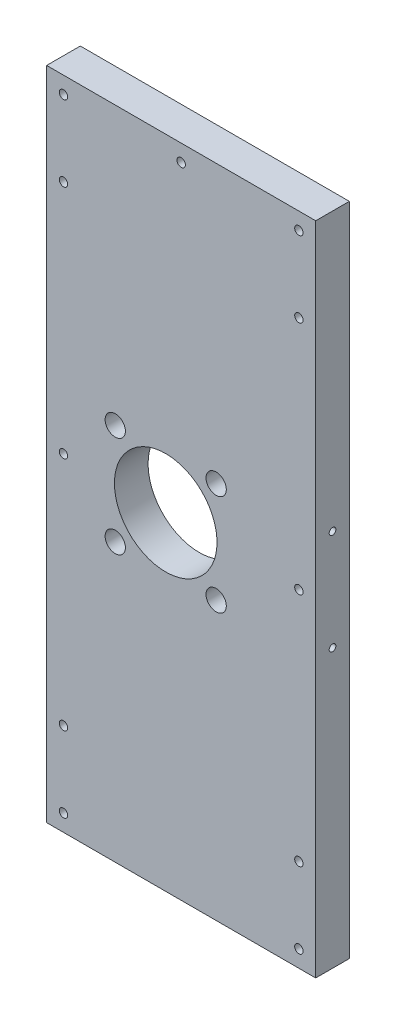
SolidWorks part; units mm, degrees
ref_plane "Ebene vorne" through (0, 0, 0) normal (0, 0, 1) x (1, 0, 0)
ref_plane "Ebene oben" through (0, 0, 0) normal (0, 1, 0) x (1, 0, 0)
ref_plane "Ebene rechts" through (0, 0, 0) normal (1, 0, 0) x (0, 0, -1)
sketch "Skizze1" plane through (0, 0, 0) normal (0, 0, 1) x (1, 0, 0)
  line L1 (-69.0594, 70.0995) -> (10.9406, 70.0995)
  line L2 (-69.0594, 70.0995) -> (-69.0594, -124.9005)
  line L3 (-69.0594, -124.9005) -> (10.9406, -124.9005)
  line L4 (10.9406, 70.0995) -> (10.9406, -124.9005)
  dimension "D1" = 195
  dimension "D2" = 80
extrude "Aufsatz-Linear austragen1" add sketch "Skizze1" against normal blind 10
sketch "Skizze2" plane through (0, 0, -10) normal (0, 0, -1) x (-1, 0, 0)
  line L0 (33.6594, 70.0995) -> (33.6594, -124.9005) construction
  line L1 (-10.9406, 70.0995) -> (69.0594, 70.0995) construction
  line L2 (69.0594, -124.9005) -> (-10.9406, -124.9005) construction
  line L3 (33.6594, -27.4005) -> (69.0594, -27.4005) construction
  line L4 (69.0594, 70.0995) -> (69.0594, -124.9005) construction
  line L5 (18.6594, -12.4005) -> (48.6594, -12.4005) construction
  line L6 (48.6594, -12.4005) -> (48.6594, -42.4005) construction
  line L7 (48.6594, -42.4005) -> (18.6594, -42.4005) construction
  line L8 (18.6594, -42.4005) -> (18.6594, -12.4005) construction
  line L9 (18.6594, -12.4005) -> (48.6594, -42.4005) construction
  circle A0 centre (18.6594, -12.4005) radius 3.015
  circle A1 centre (48.6594, -12.4005) radius 3.015
  circle A2 centre (18.6594, -42.4005) radius 3.015
  circle A3 centre (48.6594, -42.4005) radius 3.015
  circle A4 centre (33.6594, -27.4005) radius 15.25
  point P22 (33.6594, -27.4005)
  dimension "D1" = 30
  dimension "D3" = 6.03
  dimension "D2" = 30
  dimension "D4" = 35.4
extrude "Schnitt-Linear austragen1" cut sketch "Skizze2" against normal blind 10
sketch "Skizze3" plane through (0, 0, -10) normal (0, 0, -1) x (-1, 0, 0)
  line L0 (-5.9406, 65.0995) -> (64.0594, 65.0995) construction
  line L1 (29.0594, 65.0995) -> (29.0594, 70.0995) construction
  line L2 (-10.9406, 70.0995) -> (69.0594, 70.0995) construction
  line L3 (69.0594, 70.0995) -> (69.0594, -124.9005) construction
  line L4 (-5.9406, -119.9005) -> (64.0594, -119.9005) construction
  line L5 (29.0594, -119.9005) -> (29.0594, -124.9005) construction
  line L6 (69.0594, -124.9005) -> (-10.9406, -124.9005) construction
  line L7 (-5.9406, 42.5995) -> (-5.9406, -27.4005) construction
  line L8 (-5.9406, 42.5995) -> (-5.9406, 65.0995) construction
  line L9 (-5.9406, -27.4005) -> (-5.9406, -97.4005) construction
  line L10 (64.0594, 42.5995) -> (64.0594, 65.0995) construction
  line L11 (64.0594, -97.4005) -> (64.0594, -27.4005) construction
  line L12 (-5.9406, -97.4005) -> (-5.9406, -119.9005) construction
  line L13 (64.0594, -97.4005) -> (64.0594, -119.9005) construction
  line L15 (64.0594, -27.4005) -> (64.0594, 42.5995) construction
  circle A0 centre (29.0594, 65.0995) radius 2.5
  circle A1 centre (-5.9406, 65.0995) radius 2.5
  circle A2 centre (64.0594, 65.0995) radius 2.5
  circle A3 centre (29.0594, -119.9005) radius 2.5
  circle A4 centre (-5.9406, -119.9005) radius 2.5
  circle A5 centre (64.0594, -119.9005) radius 2.5
  circle A6 centre (-5.9406, 42.5995) radius 2.5
  circle A7 centre (-5.9406, -27.4005) radius 2.5
  circle A9 centre (-5.9406, -97.4005) radius 2.5
  circle A10 centre (64.0594, -97.4005) radius 2.5
  circle A12 centre (64.0594, -27.4005) radius 2.5
  circle A13 centre (64.0594, 42.5995) radius 2.5
  dimension "D3" = 5
  dimension "D1" = 5
  dimension "D2" = 5
  dimension "D4" = 70
extrude "Schnitt-Linear austragen2" cut sketch "Skizze3" against normal blind 5
sketch "Skizze6" plane through (0, 0, 0) normal (0, 0, 1) x (1, 0, 0)
  line L0 (-64.0594, 65.0995) -> (-64.0594, 42.5995) construction
  line L2 (-64.0594, 42.5995) -> (-64.0594, -27.4005) construction
  line L3 (-64.0594, -27.4005) -> (-64.0594, -97.4005) construction
  line L4 (-64.0594, -97.4005) -> (-64.0594, -119.9005) construction
  line L5 (-64.0594, 65.0995) -> (5.9406, 65.0995) construction
  line L6 (5.9406, -119.9005) -> (5.9406, -97.4005) construction
  line L7 (5.9406, -97.4005) -> (5.9406, -27.4005) construction
  line L8 (5.9406, -27.4005) -> (5.9406, 42.5995) construction
  line L10 (5.9406, 42.5995) -> (5.9406, 65.0995) construction
  line L11 (-64.0594, -119.9005) -> (5.9406, -119.9005) construction
  line L12 (10.9406, 70.0995) -> (-69.0594, 70.0995) construction
  line L14 (-29.0594, 65.0995) -> (-29.0594, 70.0995) construction
  line L15 (-69.0594, -124.9005) -> (10.9406, -124.9005) construction
  circle A0 centre (-64.0594, 65.0995) radius 1.25
  circle A1 centre (-29.0594, 65.0995) radius 1.25
  circle A2 centre (5.9406, 65.0995) radius 1.25
  circle A3 centre (-64.0594, 42.5995) radius 1.25
  circle A5 centre (-64.0594, -27.4005) radius 1.25
  circle A6 centre (-64.0594, -97.4005) radius 1.25
  circle A7 centre (-64.0594, -119.9005) radius 1.25
  circle A8 centre (5.9406, -119.9005) radius 1.25
  circle A9 centre (5.9406, -97.4005) radius 1.25
  circle A10 centre (5.9406, -27.4005) radius 1.25
  circle A12 centre (5.9406, 42.5995) radius 1.25
  dimension "D2" = 2.5
  dimension "D1" = 5
  dimension "D3" = 5
  dimension "D4" = 70
extrude "Schnitt-Linear austragen4" cut sketch "Skizze6" against normal blind 5
sketch "Skizze7" plane through (-69.0594, 0, 0) normal (-1, 0, 0) x (0, 0, 1)
  line L0 (0, -27.4005) -> (-10, -27.4005) construction
  line L1 (0, 70.0995) -> (0, -124.9005) construction
  line L2 (-10, 70.0995) -> (-10, -124.9005) construction
  line L3 (-5, -27.4005) -> (-5, -42.4005) construction
  line L4 (-5, -27.4005) -> (-5, -12.4005) construction
  circle A0 centre (-5, -12.4005) radius 1
  circle A1 centre (-5, -42.4005) radius 1
  dimension "D1" = 2
  dimension "D2" = 30
extrude "Schnitt-Linear austragen5" cut sketch "Skizze7" against normal blind 20
sketch "Skizze8" plane through (10.9406, 0, 0) normal (1, 0, 0) x (0, 0, -1)
  line L0 (10, -27.4005) -> (0, -27.4005) construction
  line L1 (5, -27.4005) -> (5, -42.4005) construction
  line L2 (5, -27.4005) -> (5, -12.4005) construction
  line L3 (0, -124.9005) -> (0, 70.0995) construction
  line L4 (10, -124.9005) -> (10, 70.0995) construction
  circle A0 centre (5, -12.4005) radius 1
  circle A1 centre (5, -42.4005) radius 1
  point P7 (0, -27.4005)
  point P10 (10, -27.4005)
  dimension "D1" = 2
  dimension "D2" = 30
extrude "Schnitt-Linear austragen6" cut sketch "Skizze8" against normal blind 30
